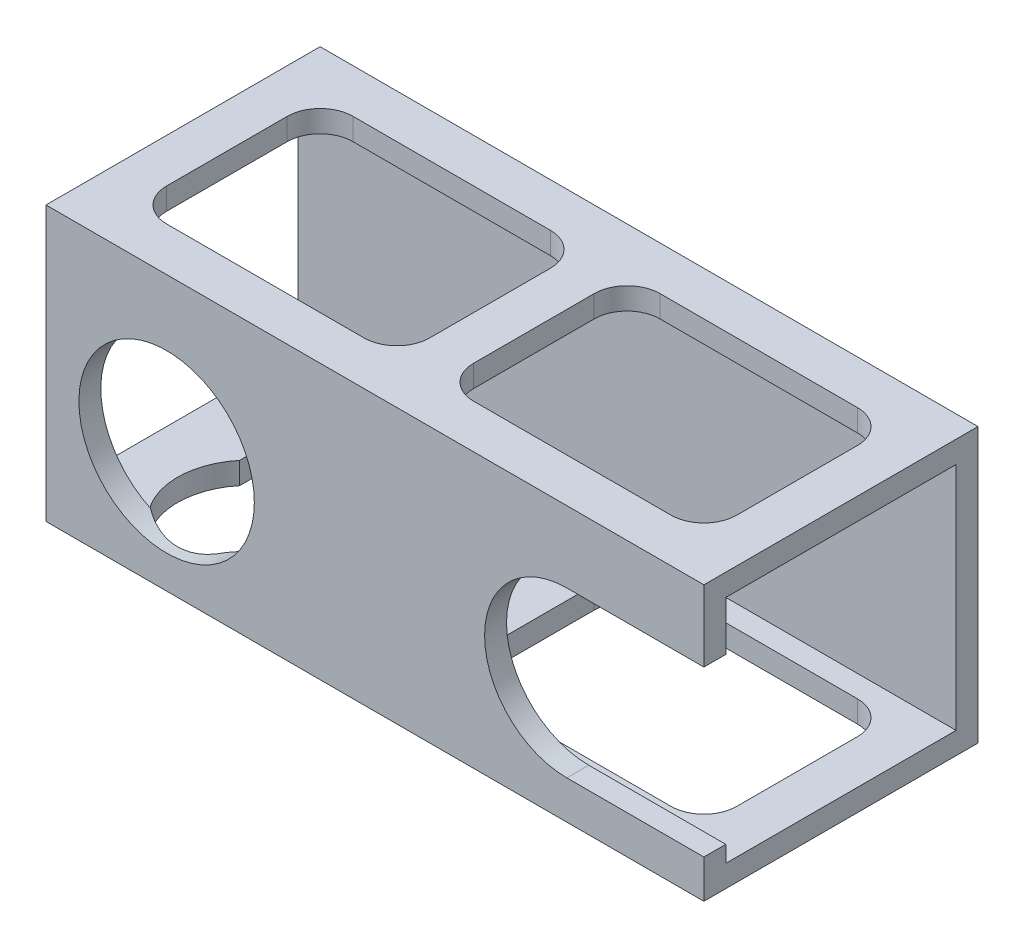
SolidWorks part; units mm, degrees
material "6063-T1"
ref_plane "Front" through (0, 0, 0) normal (0, 0, 1) x (1, 0, 0)
ref_plane "Top" through (0, 0, 0) normal (0, 1, 0) x (1, 0, 0)
ref_plane "Right" through (0, 0, 0) normal (1, 0, 0) x (0, 0, -1)
sketch "Эскиз1" plane through (0, 0, 0) normal (1, 0, 0) x (0, 0, -1)
  line L0 (0, 25) -> (0, 0)
  line L1 (0, 0) -> (25, 0)
  line L2 (2, 23) -> (2, 2)
  line L3 (2, 2) -> (23, 2)
  line L4 (2, 25) -> (2, 2) construction
  line L5 (0, 0) -> (23, 0) construction
  line L6 (2, 23) -> (23, 23)
  line L7 (23, 23) -> (23, 2)
  line L8 (0, 25) -> (25, 25)
  line L9 (25, 25) -> (25, 0)
  dimension "D2" = 2
  dimension "D3" = 2
  dimension "D4" = 25
  dimension "D5" = 25
  dimension "D1" = 2
extrude "Бобышка-Вытянуть1" add sketch "Эскиз1" along normal blind 60 contours L3 L2 L0 L1 region at (0, 24.6464, -12.5)
sketch "Эскиз2" plane through (0, 0, 0) normal (0, 0, 1) x (1, 0, 0)
  line L0 (60, 0) -> (0, 0) construction
  line L1 (0, 25) -> (0, 0) construction
  line L2 (60, 25) -> (60, 0) construction
  circle A0 centre (11, 11) radius 8
  circle A1 centre (47.5, 11) radius 7.5
  dimension "D1" = 16
  dimension "D2" = 11
  dimension "D4" = 15
  dimension "D5" = 12.5
  dimension "D3" = 11
  dimension "D6" = 11
extrude "Вырез-Вытянуть1" cut sketch "Эскиз2" against normal up to next
sketch "Эскиз3" plane through (0, 0, 0) normal (0, -1, 0) x (1, 0, 0)
  line L1 (0, 0) -> (0, -25) construction
  line L2 (60, 0) -> (0, 0) construction
  circle A0 centre (11, -7.5) radius 6.5
  dimension "D1" = 13
  dimension "D2" = 7.5
  dimension "D3" = 11
extrude "Вырез-Вытянуть2" cut sketch "Эскиз3" against normal blind 4.5
sketch "Эскиз4" plane through (0, 0, 0) normal (0, 1, 0) x (1, 0, 0)
  line L0 (16, 25) -> (16, 11.6533)
  line L2 (6, 25) -> (6, 11.6533)
  line L3 (60, 25) -> (0, 25) construction
  arc A0 (14.4641, 2) -> (7.5359, 2) centre (11, 7.5) ccw construction
  circle M13 centre (11, 7.5) radius 6.5
  line M15 (0, 25) -> (60, 25)
  dimension "D1" = 10
extrude "Вырез-Вытянуть3" cut sketch "Эскиз4" along normal blind 2.5 contours L2 L0 M15 M13 region at (11, 0, -19.1229)
sketch "Эскиз5" plane through (0, 0, 0) normal (0, 0, 1) x (1, 0, 0)
  line L0 (47.5, 18.5) -> (60, 18.5)
  line L2 (60, 25) -> (60, 0) construction
  line L3 (47.5, 3.5) -> (60, 3.5)
  circle A1 centre (47.5, 11) radius 7.5 construction
  circle M1 centre (47.5, 11) radius 7.5
  line M5 (60, 0) -> (60, 25)
extrude "Вырез-Вытянуть4" cut sketch "Эскиз5" against normal up to next contours L3 L0 M1 M5 region at (56.4833, 11, 0)
sketch "Эскиз6" plane through (0, 25, 0) normal (0, 1, 0) x (1, 0, 0)
  line L0 (0, 12.5) -> (60, 12.5) construction
  line L1 (7, 4) -> (25, 4)
  line L2 (4, 7) -> (4, 18)
  line L3 (7, 21) -> (25, 21)
  line L4 (28, 7) -> (28, 18)
  line L5 (4, 4) -> (28, 21) construction
  line L6 (4, 21) -> (28, 4) construction
  line L7 (0, 0) -> (0, 25) construction
  line L8 (60, 0) -> (60, 25) construction
  line L9 (30, 25) -> (30, 0) construction
  line L10 (60, 25) -> (0, 25) construction
  line L11 (60, 0) -> (0, 0) construction
  line L12 (32, 7) -> (32, 18)
  line L13 (53, 4) -> (35, 4)
  line L14 (56, 7) -> (56, 18)
  line L15 (53, 21) -> (35, 21)
  arc A0 (7, 4) -> (4, 7) centre (7, 7) cw
  arc A1 (25, 4) -> (28, 7) centre (25, 7) ccw
  arc A2 (28, 18) -> (25, 21) centre (25, 18) ccw
  arc A3 (7, 21) -> (4, 18) centre (7, 18) ccw
  arc A4 (32, 18) -> (35, 21) centre (35, 18) cw
  arc A5 (35, 4) -> (32, 7) centre (35, 7) cw
  arc A6 (53, 4) -> (56, 7) centre (53, 7) ccw
  arc A7 (53, 21) -> (56, 18) centre (53, 18) cw
  point P0 (16, 12.5)
  dimension "D1" = 3
  dimension "D2" = 24
  dimension "D3" = 17
  dimension "D4" = 4
extrude "Вырез-Вытянуть5" cut sketch "Эскиз6" against normal up to next contours L3 A3 L2 A0 L1 A1 L4 A2 | A7 L15 A4 L12 A5 L13 A6 L14 region at (16, 25, -12.5) region at (44, 25, -12.5)
extrude "Вырез-Вытянуть6" cut sketch "Эскиз6<3>" against normal up to next contours A7 L15 A4 L12 A5 L13 A6 L14 region at (44, 25, -12.5)
sketch "Эскиз6<3>" plane through (0, 25, 0) normal (0, 1, 0) x (1, 0, 0) same geometry as "Эскиз6"
